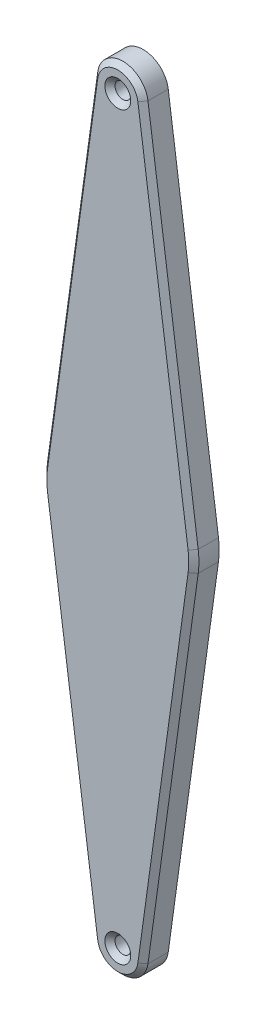
SolidWorks part; units mm, degrees
ref_plane "Front Plane" through (0, 0, 0) normal (0, 0, 1) x (1, 0, 0)
ref_plane "Top Plane" through (0, 0, 0) normal (0, 1, 0) x (1, 0, 0)
ref_plane "Right Plane" through (0, 0, 0) normal (1, 0, 0) x (0, 0, -1)
sketch "Sketch1" plane through (0, 0, 0) normal (0, 0, 1) x (1, 0, 0)
  line L1 (191, 68) -> (85, 68)
  line L2 (85, 68) -> (85, 141) construction
  line L3 (89.9529, 141.6849) -> (99.8586, 70.0548)
  line L8 (0, 136) -> (0, 0)
  line L9 (0, 0) -> (191, 0)
  line L10 (191, 0) -> (191, 136)
  line L11 (191, 136) -> (0, 136)
  line L12 (80.0471, 141.6849) -> (70.1414, 70.0548)
  line L13 (89.9529, -5.6849) -> (99.8586, 65.9452)
  line L14 (80.0471, -5.6849) -> (70.1414, 65.9452)
  circle A0 centre (85, 68) radius 15
  circle A1 centre (85, 141) radius 5
  circle A2 centre (85, -5) radius 5
  dimension "D2" = 30
  dimension "D4" = 10
  dimension "D3" = 5
extrude "Boss-Extrude1" add sketch "Sketch1" along normal blind 5 contours L2 A0 L3 L11 | A0 L2 L11 L12 | A1 | A1 L11 L3 | A1 L12 L11 | L1 L2 A0 | L2 L1 A0 | A0 L14 L9 L13 | L14 A2 L9 | L9 A2 L13 | A2 region at (82.8779, 65.8779, 0) region at (91.3662, 74.3662, 0) region at (90.3088, 104.3689, 0) region at (85, 31.6311, 0) region at (89.2502, -1.2971, 0) region at (89.2502, 137.2971, 0) region at (79.6912, 104.3689, 0) region at (80.7498, -1.2971, 0) region at (85, -5, 0) region at (89.8471, 141.3336, 0) region at (80.7498, 137.2971, 0)
chamfer "Chamfer1" distance 1 angle 45 8 edges at (75.0943, 30.1301, 5) (70, 68, 5) (75.0943, 105.8699, 5) (85, 146, 5) (94.9057, 105.8699, 5) (100, 68, 5) (94.9057, 30.1301, 5) (85, -10, 5)
sketch "Sketch6" plane through (0, 0, 5) normal (0, 0, 1) x (1, 0, 0)
  circle A0 centre (85, 141) radius 1.55
  dimension "D1" = 3.1
extrude "Cut-Extrude2" cut sketch "Sketch6" against normal up to next contours A0 region at (85, 141, 5)
chamfer "Chamfer3" distance 1 angle 45 1 edges at (86.55, 141, 5)
sketch "Sketch7" plane through (0, 0, 5) normal (0, 0, 1) x (1, 0, 0)
  line L1 (190.9943, 69.0969) -> (85, 68) construction
  line L2 (190.9943, 69.0969) -> (85, 68) construction
ref_axis "Axis2" through (99, 68, 5) along (-1, 0, 0)
sketch "Sketch8" plane through (0, 0, 0) normal (0, 0, -1) x (-1, 0, 0)
  line L0 (-100, 68) -> (-70, 68) construction
  arc A0 (-99.8586, 70.0548) -> (-99.8586, 65.9452) centre (-85, 68) ccw construction
  arc A1 (-70.1414, 65.9452) -> (-70.1414, 70.0548) centre (-85, 68) ccw construction
ref_axis "Axis3" through (100, 68, 0) along (-1, 0, 0)
ref_plane "Plane3" through (0, 68, 0) normal (0, -1, 0) x (-1, 0, 0)
mirror "Mirror2" about plane through (0, 68, 0) normal (0, -1, 0) of "Cut-Extrude2", "Chamfer3"
sketch "Sketch9" plane through (0, 0, 0) normal (0, 0, -1) x (-1, 0, 0)
  line L0 (-100, 68) -> (-70, 68) construction
  arc A0 (-99.8586, 70.0548) -> (-99.8586, 65.9452) centre (-85, 68) ccw construction
  arc A1 (-70.1414, 65.9452) -> (-70.1414, 70.0548) centre (-85, 68) ccw construction
  point P8 (-85, 68)
ref_point "Point1"
